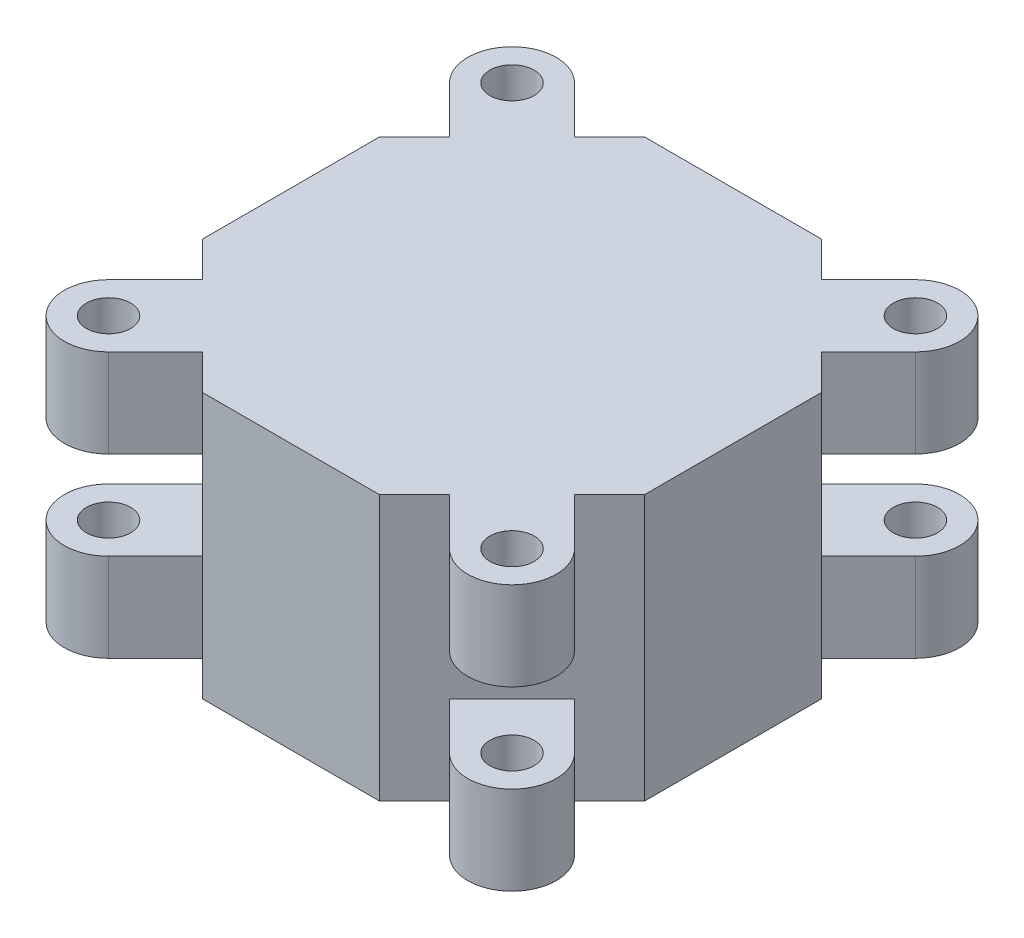
SolidWorks part; units mm, degrees
ref_plane "Front Plane" through (0, 0, 0) normal (0, 0, 1) x (1, 0, 0)
ref_plane "Top Plane" through (0, 0, 0) normal (0, 1, 0) x (1, 0, 0)
ref_plane "Right Plane" through (0, 0, 0) normal (1, 0, 0) x (0, 0, -1)
ref_axis "X" through (-88.99, 0, 0) along (1, 0, 0)
ref_axis "Y" through (0, 55, 0) along (0, -1, 0)
ref_axis "Z" through (0, 0, -88.99) along (0, 0, 1)
sketch "Sketch1" plane through (0, 0, 0) normal (0, 1, 0) x (1, 0, 0)
  line L0 (20, -50) -> (50, -20)
  line L1 (-50, 50) -> (50, 50)
  line L2 (-50, 50) -> (-50, -50)
  line L3 (-50, -50) -> (50, -50)
  line L4 (50, 50) -> (50, -50)
  line L5 (-50, 50) -> (50, -50) construction
  line L6 (-50, -50) -> (50, 50) construction
  line L7 (50, 20) -> (20, 50)
  line L8 (-20, 50) -> (-50, 20)
  line L11 (-50, -20) -> (-20, -50)
  point P0 (0, 0)
  dimension "D1" = 100
  dimension "D2" = 100
  dimension "D3" = 45
  dimension "D4" = 30
extrude "Boss-Extrude1" add sketch "Sketch1" along normal blind 60 contours L2 L11 L3 L0 L4 L7 L1 L8 region at (0, 0, 0)
sketch "Sketch2" plane through (0, 0, 0) normal (0, 1, 0) x (1, 0, 0)
  line L0 (20, -50) -> (50, -20) construction
  line L1 (20, -50) -> (50, -20)
  line L2 (27.9289, -42.0711) -> (38.5355, -52.6777)
  line L3 (52.6777, -38.5355) -> (42.0711, -27.9289)
  line L4 (45.6066, -45.6066) -> (35, -35) construction
  arc A0 (38.5355, -52.6777) -> (52.6777, -38.5355) centre (45.6066, -45.6066) ccw
  circle A1 centre (45.6066, -45.6066) radius 5
  dimension "D1" = 5
  dimension "D2" = 10
  dimension "D3" = 15
extrude "Boss-Extrude2" add sketch "Sketch2" along normal blind 20 contours A1 L1 L2 A0 L3 region at (35.2768, 0, 35.2768)
extrude "Boss-Extrude3" add sketch "Sketch2<3>" against normal offset from surface (20 mm away) 20 from surface contours A1 L1 L2 A0 L3 region at (35.2768, 0, 35.2768) up to face at (42.0711, 20, 42.0711) starting at face at (0, 60, 0)
sketch "Sketch2<3>" plane through (0, 0, 0) normal (0, 1, 0) x (1, 0, 0) same geometry as "Sketch2"
pattern_circular "CirPattern1" count 4 every 90 about axis through (0, 55, 0) along (0, -1, 0) of "Boss-Extrude3", "Boss-Extrude2"
